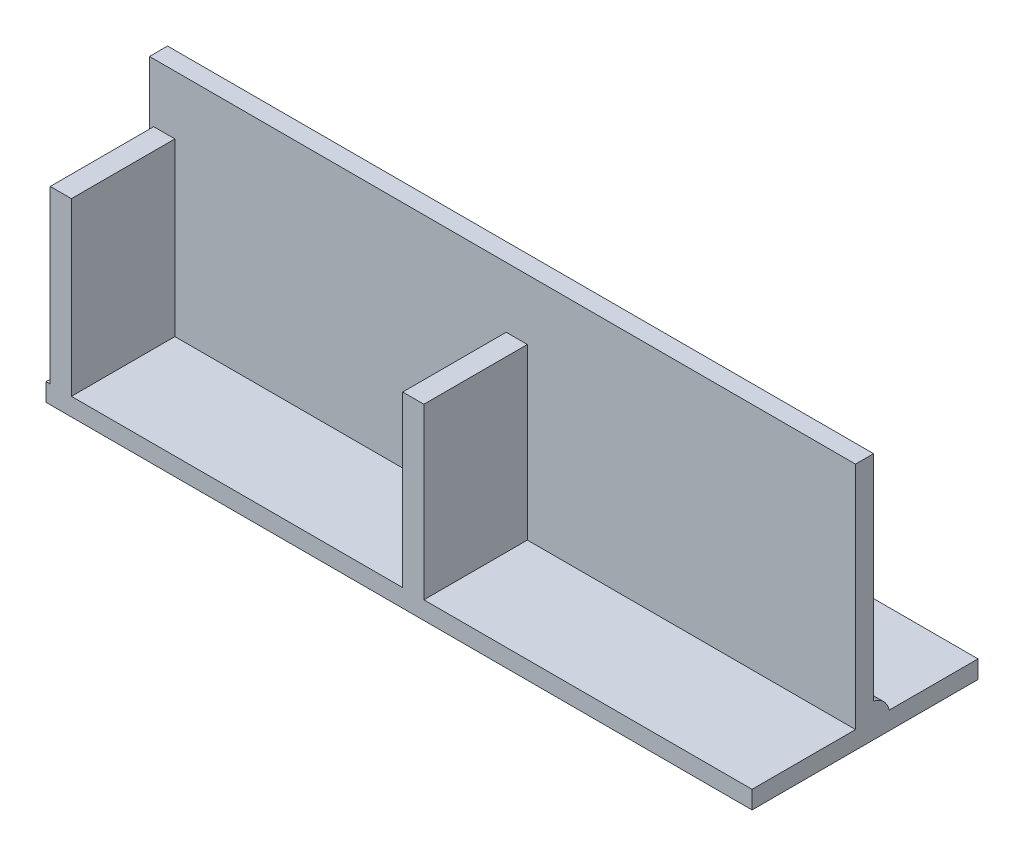
SolidWorks part; units mm, degrees
ref_plane "Front Plane" through (0, 0, 0) normal (0, 0, 1) x (1, 0, 0)
ref_plane "Top Plane" through (0, 0, 0) normal (0, 1, 0) x (1, 0, 0)
ref_plane "Right Plane" through (0, 0, 0) normal (1, 0, 0) x (0, 0, -1)
sketch "Sketch1" plane through (0, 0, 0) normal (0, 1, 0) x (1, 0, 0)
  line L1 (0, 0) -> (317.5, 0)
  line L2 (0, 0) -> (0, 101.6)
  line L3 (0, 101.6) -> (317.5, 101.6)
  line L4 (317.5, 0) -> (317.5, 101.6)
  dimension "D1" = 317.5
  dimension "D2" = 101.6
extrude "Boss-Extrude1" add sketch "Sketch1" along normal blind 8.0518
sketch "Sketch2" plane through (0, 0, 0) normal (0, 1, 0) x (1, 0, 0)
  line L0 (0, 101.6) -> (0, 0) construction
  line L1 (0, 54.6608) -> (317.5, 54.6608)
  line L2 (0, 54.6608) -> (0, 46.5328)
  line L3 (0, 46.5328) -> (317.5, 46.5328)
  line L4 (317.5, 54.6608) -> (317.5, 46.5328)
  line L5 (317.5, 0) -> (317.5, 101.6) construction
  dimension "D1" = 8.128
  dimension "D2" = 46.5328
extrude "Boss-Extrude2" add sketch "Sketch2" along normal blind 103.378 from surface starting at face at (158.75, 8.0518, -50.8)
sketch "Sketch3" plane through (0, 0, 0) normal (0, 1, 0) x (1, 0, 0)
  line L0 (0, 46.5328) -> (317.5, 46.5328) construction
  line L1 (1.905, 0) -> (11.43, 0)
  line L2 (1.905, 0) -> (1.905, 46.5328)
  line L3 (1.905, 46.5328) -> (11.43, 46.5328)
  line L4 (11.43, 0) -> (11.43, 46.5328)
  line L5 (0, 0) -> (317.5, 0) construction
  line L6 (160.401, 0) -> (169.926, 0)
  line L7 (160.401, 0) -> (160.401, 46.5328)
  line L8 (160.401, 46.5328) -> (169.926, 46.5328)
  line L9 (169.926, 0) -> (169.926, 46.5328)
  point P13 (1.3493, 0)
  dimension "D1" = 9.525
  dimension "D2" = 9.525
  dimension "D3" = 148.971
  dimension "D4" = 1.905
extrude "Boss-Extrude3" add sketch "Sketch3" along normal blind 76.9874 from surface contours L1 L4 L3 L2 starting at face at (158.75, 8.0518, -23.2664)
extrude "Boss-Extrude4" add sketch "Sketch3<3>" along normal blind 76.1746 from surface contours L9 L8 L7 L6 starting at face at (164.465, 8.0518, -23.2664)
sketch "Sketch3<3>" plane through (0, 0, 0) normal (0, 1, 0) x (1, 0, 0) same geometry as "Sketch3"
sketch "Sketch4" plane through (0, 0, 0) normal (1, 0, 0) x (0, 0, -1)
  line L1 (54.6608, 111.4298) -> (54.6608, 8.0518) construction
  line L2 (54.6608, 8.0518) -> (101.6, 8.0518) construction
  line L3 (61.6458, 8.0518) -> (54.6608, 8.0518)
  line L4 (54.6608, 8.0518) -> (54.6608, 15.0368)
  arc A0 (54.6608, 15.0368) -> (61.6458, 8.0518) centre (52.8547, 6.2457) cw
  point P10 (61.4904, 8.0518)
  dimension "D1" = 6.985
extrude "Boss-Extrude5" add sketch "Sketch4" along normal up to surface (317.5 mm away) up to face at (317.5, 31.8833, -50.6984)
equation "\"length\"=12.5"
equation "\"D1@Sketch1\"=\"length\""
equation "\"width\"=4"
equation "\"D2@Sketch1\"=\"width\""
